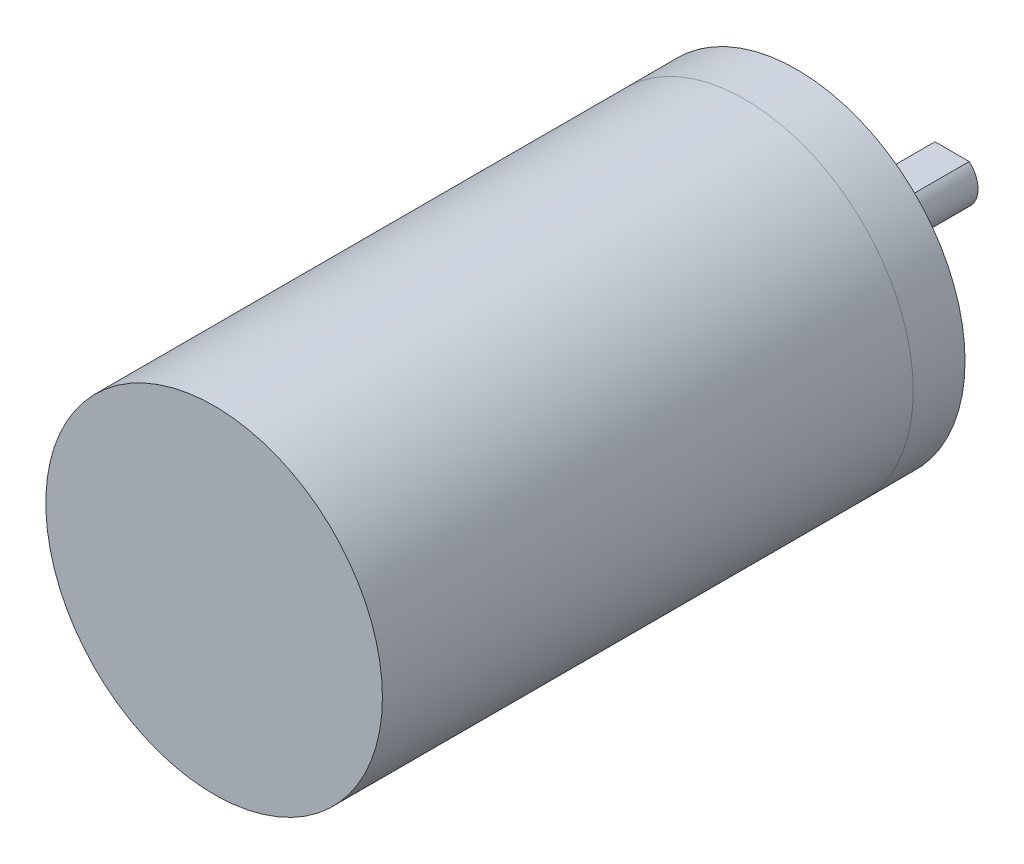
SolidWorks part; units mm, degrees
ref_plane "Front Plane" through (0, 0, 0) normal (0, 0, 1) x (1, 0, 0)
ref_plane "Top Plane" through (0, 0, 0) normal (0, 1, 0) x (1, 0, 0)
ref_plane "Right Plane" through (0, 0, 0) normal (1, 0, 0) x (0, 0, -1)
sketch "Sketch1" plane through (0, 0, 0) normal (0, 0, 1) x (1, 0, 0)
  circle A0 centre (0, 0) radius 13
  dimension "D1" = 26
extrude "Motor Body" add sketch "Sketch1" along normal blind 45
sketch "Sketch2" plane through (0, 0, 0) normal (0, 0, 1) x (1, 0, 0)
  line L0 (10, 0) -> (-10, 0) construction
  line L1 (1.3229, 1.5) -> (-1.3229, 1.5)
  line L2 (0, 10) -> (0, -10) construction
  circle A2 centre (0, 0) radius 2
  point P11 (0, 0)
  point P13 (0, 0)
  dimension "D2" = 4
  dimension "D1" = 20
  dimension "D3" = 1.5
extrude "Boss-Extrude2" add sketch "Sketch2" against normal blind 12 contours L1 A2 region at (0, -0.1324, 0)
extrude "Boss-Extrude3" add sketch "Sketch2<3>" against normal offset from surface (4 mm away) 8 contours L1 A2 region at (0, 1.7023, 0) up to face at (0, -0.25, -12)
sketch "Sketch2<3>" plane through (0, 0, 0) normal (0, 0, 1) x (1, 0, 0) same geometry as "Sketch2"
hole_wizard "Ø3.0mm Dowel Hole2" positions "Sketch5" profile "Sketch6" hole size "Ø3.0" standard "ANSI Metric"
sketch "Sketch5" plane through (0, 0, 0) normal (0, 0, -1) x (-1, 0, 0)
  point P0 (-10, 0)
  point P3 (10, 0)
sketch "Sketch6" plane through (10, 0, 0) normal (1, 0, 0) x (0, 1, 0)
  line L0 (0, 0) -> (0, 5.9013)
  line L1 (0, 5.9013) -> (1.5, 5)
  line L2 (1.5, 5) -> (1.5, 0)
  line L5 (1.5, 0) -> (0, 0)
  line L10 (0, 5.9013) -> (-1.5, 5) construction
  line L11 (0, -6.35) -> (0, 107.95) construction
  dimension "Hole Dia." = 3
  dimension "Hole Depth" = 5
  dimension "Drill Angle" = 118
sketch "Sketch7" plane through (0, 0, 0) normal (0, 1, 0) x (1, 0, 0)
  line L0 (-13, -4) -> (13, -4)
  line L1 (-13, 0) -> (-13, -45) construction
  line L2 (13, -45) -> (13, 0) construction
  line L3 (13, 0) -> (-13, 0) construction
  point P6 (-13, -4.3884)
  dimension "D1" = 4
split line "Split Line1"
